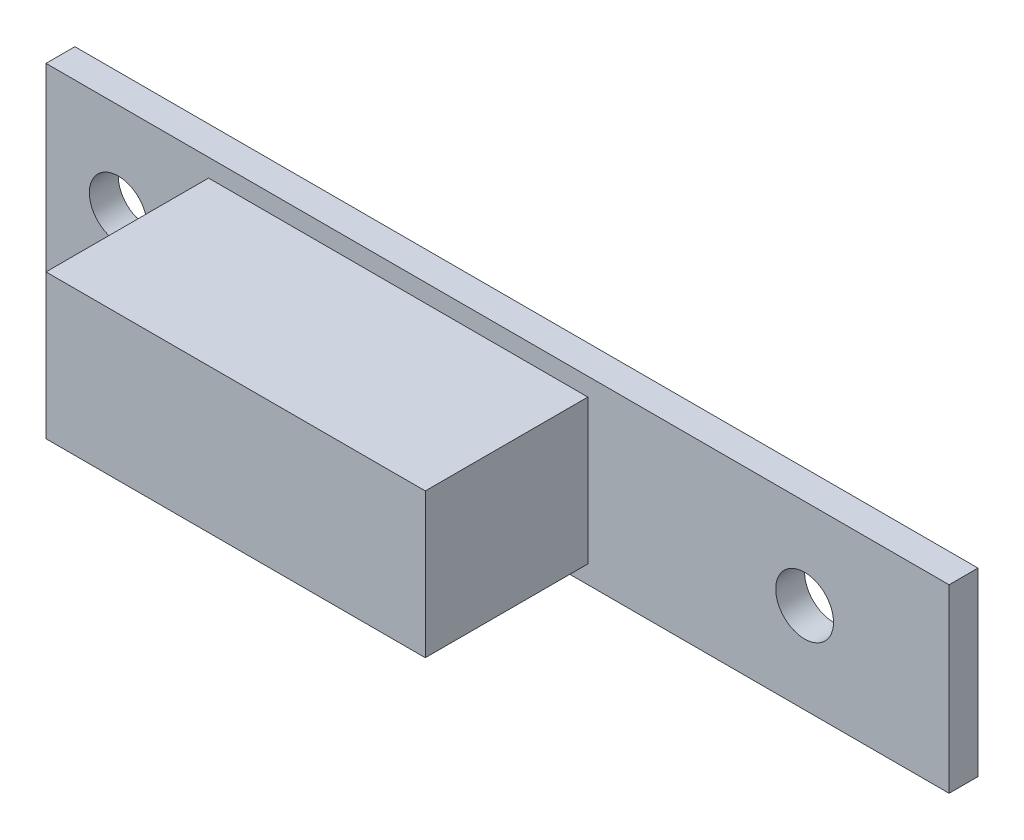
SolidWorks part; units mm, degrees
ref_plane "Front Plane" through (0, 0, 0) normal (0, 0, 1) x (1, 0, 0)
ref_plane "Top Plane" through (0, 0, 0) normal (0, 1, 0) x (1, 0, 0)
ref_plane "Right Plane" through (0, 0, 0) normal (1, 0, 0) x (0, 0, -1)
sketch "Sketch1" plane through (0, 0, 0) normal (0, 0, 1) x (1, 0, 0)
  line L0 (0, 5) -> (50000, 5) construction
  line L1 (0, 0) -> (50, 0)
  line L2 (0, 0) -> (0, 10)
  line L3 (0, 10) -> (50, 10)
  line L4 (50, 0) -> (50, 10)
  circle A0 centre (4, 5) radius 1.6
  circle A1 centre (42, 5) radius 1.6
  point P7 (0, 5)
  dimension "D3" = 3.2
  dimension "D1" = 50
  dimension "D2" = 10
  dimension "D4" = 4
  dimension "D5" = 8
extrude "Boss-Extrude1" add sketch "Sketch1" along normal blind 1.6
sketch "Sketch2" plane through (0, 0, 1.6) normal (0, 0, 1) x (1, 0, 0)
  line L0 (0, 5) -> (50000, 5) construction
  line L1 (9, 9) -> (30, 9)
  line L2 (9, 9) -> (9, 1)
  line L3 (9, 1) -> (30, 1)
  line L4 (30, 9) -> (30, 1)
  line L5 (0, 10) -> (0, 0) construction
  point P8 (0, 5)
  dimension "D1" = 8
  dimension "D2" = 21
  dimension "D3" = 9
extrude "Boss-Extrude2" add sketch "Sketch2" along normal blind 9
